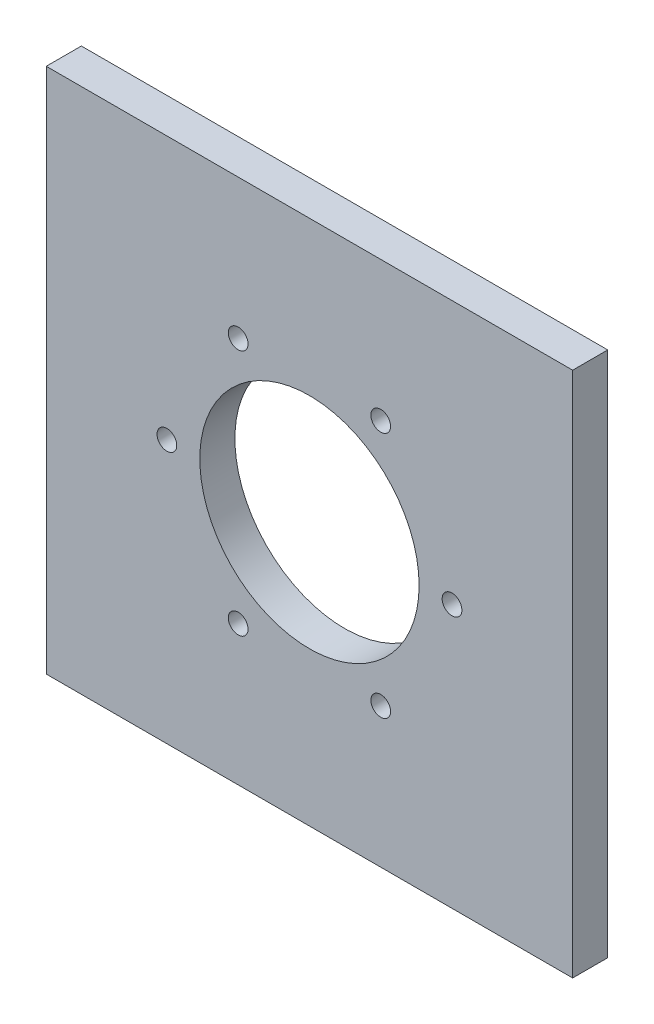
SolidWorks part; units mm, degrees
material "Alumina"
ref_plane "Front Plane" through (0, 0, 0) normal (0, 0, 1) x (1, 0, 0)
ref_plane "Top Plane" through (0, 0, 0) normal (0, 1, 0) x (1, 0, 0)
ref_plane "Right Plane" through (0, 0, 0) normal (1, 0, 0) x (0, 0, -1)
sketch "Sketch1" plane through (0, 0, 0) normal (0, 0, 1) x (1, 0, 0)
  line L1 (-60, 60) -> (60, 60)
  line L2 (-60, 60) -> (-60, -60)
  line L3 (-60, -60) -> (60, -60)
  line L4 (60, 60) -> (60, -60)
  line L5 (-60, 60) -> (60, -60) construction
  line L6 (-60, -60) -> (60, 60) construction
  circle A0 centre (0, 0) radius 25
  point P0 (0, 0)
  dimension "D3" = 50
  dimension "D1" = 120
  dimension "D2" = 120
extrude "Boss-Extrude1" add sketch "Sketch1" along normal blind 8
sketch "Sketch2" plane through (0, 0, 0) normal (0, 0, 1) x (1, 0, 0)
  line L0 (0, 0) -> (0, 39.5617) construction
  line L1 (0, 39.5617) -> (0, 0) construction
  line L2 (0, 0) -> (-45.4935, 0) construction
  line L3 (-45.4935, 0) -> (48.5142, 0) construction
  line L4 (48.5142, 0) -> (0, 0) construction
  line L5 (0, 0) -> (-22.3131, 38.6473) construction
  circle A0 centre (0, 0) radius 32.5 construction
  circle A3 centre (-16.25, 28.1458) radius 2.25
  dimension "D1" = 30
extrude "Cut-Extrude2" cut sketch "Sketch2" along normal through all
pattern_circular "CirPattern1" count 6 over 360 about axis through (0, 0, 8) along (0, 0, 1) of "Cut-Extrude2"
